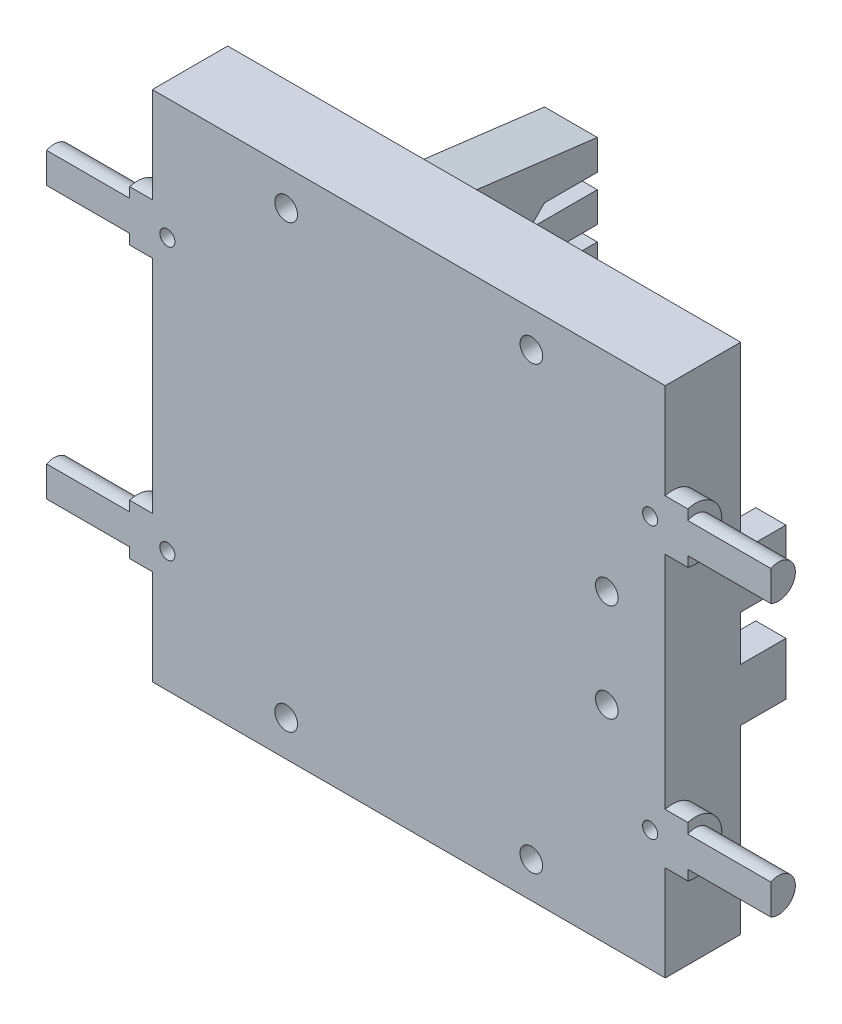
SolidWorks part; units mm, degrees
ref_plane "Front Plane" through (0, 0, 0) normal (0, 0, 1) x (1, 0, 0)
ref_plane "Top Plane" through (0, 0, 0) normal (0, 1, 0) x (1, 0, 0)
ref_plane "Right Plane" through (0, 0, 0) normal (1, 0, 0) x (0, 0, -1)
sketch "Sketch1" plane through (0, 0, 0) normal (0, 0, 1) x (1, 0, 0)
  line L1 (0, 0) -> (-68, 0)
  line L2 (0, 0) -> (0, -68)
  line L3 (0, -68) -> (-68, -68)
  line L4 (-68, 0) -> (-68, -68)
  dimension "D1" = 68
  dimension "D2" = 68
extrude "Boss-Extrude1" add sketch "Sketch1" along normal blind 10
sketch "Sketch2" plane through (-68, 0, 0) normal (-1, 0, 0) x (0, 0, 1)
  line L1 (10, 0) -> (0, 0) construction
  line L2 (10, -68) -> (0, -68) construction
  line L3 (10, 0) -> (10, -68) construction
  line L4 (10, 0) -> (10, -68)
  circle A0 centre (9, -52) radius 3.5
  circle A1 centre (9, -16) radius 3.5
  dimension "D1" = 7
  dimension "D2" = 7
  dimension "D3" = 1
  dimension "D4" = 0
  dimension "D5" = 16
  dimension "D6" = 16
extrude "Boss-Extrude2" add sketch "Sketch2" along normal blind 3 contours L4 A1 | L4 A0 region at (-68, -52, 8.0379) region at (-68, -16, 8.0379)
sketch "Sketch3" plane through (-71, 0, 0) normal (-1, 0, 0) x (0, 0, 1)
  line L0 (10, -55.3541) -> (10, -12.6459)
  circle A0 centre (9, -52) radius 2.25
  circle A1 centre (9, -16) radius 2.25
  dimension "D1" = 4.5
  dimension "D2" = 4.5
extrude "Boss-Extrude3" add sketch "Sketch3" along normal blind 11 contours L0 A0 | L0 A1 region at (-71, -52, 8.5562) region at (-71, -16, 8.5562)
sketch "Sketch4" plane through (0, 0, 0) normal (1, 0, 0) x (0, 0, -1)
  line L0 (-10, 0) -> (0, 0) construction
  line L1 (-10, -68) -> (0, -68) construction
  line L2 (-10, 0) -> (-10, -68)
  circle A0 centre (-9, -16) radius 3.5
  circle A1 centre (-9, -52) radius 3.5
  dimension "D1" = 16
  dimension "D2" = 16
  dimension "D3" = 7
  dimension "D4" = 7
  dimension "D5" = 1
  dimension "D6" = 0
extrude "Boss-Extrude4" add sketch "Sketch4" along normal blind 3 contours L2 A0 | L2 A1 region at (0, -16, 8.0379) region at (0, -52, 8.0379)
sketch "Sketch5" plane through (3, 0, 0) normal (1, 0, 0) x (0, 0, -1)
  line L0 (-10, -12.6459) -> (-10, -55.3541)
  circle A0 centre (-9, -16) radius 2.25
  circle A1 centre (-9, -52) radius 2.25
  dimension "D1" = 4.5
  dimension "D2" = 4.5
extrude "Boss-Extrude5" add sketch "Sketch5" along normal blind 11 contours L0 A0 | L0 A1 region at (3, -16, 8.5562) region at (3, -52, 8.5562)
sketch "Sketch6" plane through (0, 0, 0) normal (0, 0, -1) x (-1, 0, 0)
  line L0 (0, -34) -> (68, -34) construction
  line L1 (55.25, -12.75) -> (12.75, -12.75)
  line L2 (55.25, -12.75) -> (55.25, -55.25)
  line L3 (55.25, -55.25) -> (12.75, -55.25)
  line L4 (12.75, -12.75) -> (12.75, -55.25)
  line L5 (0, -68) -> (0, 0) construction
  line L6 (68, 0) -> (68, -68) construction
  line L7 (34, 0) -> (34, -68) construction
  line L8 (0, 0) -> (68, 0) construction
  line L9 (68, -68) -> (0, -68) construction
  point P16 (12.75, -34)
  point P17 (34, -55.25)
  dimension "D1" = 42.5
  dimension "D2" = 42.5
  dimension "D3" = 0
  dimension "D4" = 0
extrude "Cut-Extrude1" cut sketch "Sketch6" against normal blind 3
sketch "Sketch8" plane through (0, 0, 0) normal (0, 0, -1) x (-1, 0, 0)
  line L0 (55.25, -12.75) -> (12.75, -12.75) construction
  line L2 (12.75, -12.75) -> (12.75, -55.25) construction
  line L3 (34, 0) -> (34, -108.8236) construction
  line L4 (0, 0) -> (68, 0) construction
  line L5 (0, -34) -> (112.3527, -34) construction
  line L6 (0, -68) -> (0, 0) construction
  circle A0 centre (17.75, -4.75) radius 1.5
  circle A3 centre (50.25, -4.75) radius 1.5
  circle A4 centre (50.25, -63.25) radius 1.5
  circle A5 centre (17.75, -63.25) radius 1.5
  dimension "D1" = 8
  dimension "D3" = 3
  dimension "D5" = 5
extrude "Cut-Extrude2" cut sketch "Sketch8" against normal blind 15
sketch "Sketch9" plane through (0, 0, 0) normal (0, 0, -1) x (-1, 0, 0)
  line L1 (0, -24) -> (4, -24)
  line L2 (0, -24) -> (0, -31)
  line L3 (0, -31) -> (4, -31)
  line L4 (4, -24) -> (4, -31)
  line L5 (0, -68) -> (0, 0) construction
  line L6 (0, -34) -> (68, -34) construction
  line L7 (68, 0) -> (68, -68) construction
  line L8 (0, -37) -> (4, -37)
  line L9 (4, -44) -> (4, -37)
  line L10 (0, -44) -> (4, -44)
  line L11 (0, -44) -> (0, -37)
  point P6 (0, -34)
  dimension "D1" = 4
  dimension "D2" = 7
  dimension "D3" = 0
  dimension "D4" = 3
extrude "Boss-Extrude6" add sketch "Sketch9" along normal blind 6
sketch "Sketch10" plane through (0, 0, 0) normal (0, 0, -1) x (-1, 0, 0)
  line L0 (0, -34) -> (23.3312, -34) construction
  line L1 (0, -37) -> (0, -31) construction
  line L2 (12.75, -12.75) -> (12.75, -55.25) construction
  line L3 (4, -31) -> (4, -24) construction
  circle A0 centre (7.75, -27.5) radius 1.5
  circle A1 centre (7.75, -40.5) radius 1.5
  point P10 (4, -27.5)
  dimension "D1" = 3
  dimension "D2" = 5
  dimension "D3" = 0
extrude "Cut-Extrude3" cut sketch "Sketch10" against normal blind 10
sketch "Sketch11" plane through (0, 0, 10) normal (0, 0, 1) x (1, 0, 0)
  line L0 (-68, -34) -> (19.7059, -34) construction
  line L1 (-68, -19.3541) -> (-68, -48.6459) construction
  line L2 (-34, -68) -> (-34, 32.0149) construction
  line L3 (-68, -68) -> (0, -68) construction
  line L4 (-82, -54.0156) -> (-82, -49.9844) construction
  circle A0 centre (-66, -52) radius 1
  circle A1 centre (-66, -16) radius 1
  circle A2 centre (-2, -52) radius 1
  circle A3 centre (-2, -16) radius 1
  point P12 (-82, -52)
  dimension "D1" = 16
  dimension "D2" = 0
  dimension "D3" = 2
extrude "Cut-Extrude4" cut sketch "Sketch11" against normal blind 20
sketch "Sketch13" plane through (0, 0, 0) normal (0, 0, -1) x (-1, 0, 0)
  line L0 (68, 0) -> (68, -68) construction
  line L1 (59, -26) -> (66, -26)
  line L2 (59, -26) -> (59, -42)
  line L3 (59, -42) -> (66, -42)
  line L4 (66, -26) -> (66, -42)
  point P4 (66, -34)
  point P7 (68, -34)
  dimension "D1" = 7
  dimension "D2" = 0
  dimension "D3" = 16
  dimension "D4" = 2
extrude "Boss-Extrude7" add sketch "Sketch13" along normal blind 40
sketch "Sketch15" plane through (-66, 0, 0) normal (-1, 0, 0) x (0, 0, 1)
  line L0 (-40, -34) -> (24.0661, -34) construction
  line L1 (-40, -42) -> (-40, -26) construction
  line L2 (-40, -32) -> (-31, -32)
  line L3 (-31, -32) -> (-33, -30)
  line L4 (-33, -30) -> (-40, -30)
  line L5 (-40, -30) -> (-40, -32)
  line L6 (-40, -26) -> (0, -26) construction
  line L7 (-40, -38) -> (-40, -36)
  line L8 (-31, -36) -> (-33, -38)
  line L9 (-33, -38) -> (-40, -38)
  line L10 (-40, -36) -> (-31, -36)
  dimension "D1" = 2
  dimension "D2" = 4
  dimension "D3" = 45
  dimension "D4" = 7
extrude "Cut-Extrude5" cut sketch "Sketch15" against normal blind 10
sketch "Sketch16" plane through (-66, 0, 0) normal (-1, 0, 0) x (0, 0, 1)
  line L0 (0, -26) -> (-40, -26)
  line L1 (-40, -26) -> (0, -21)
  line L2 (0, -21) -> (0, -26)
  line L3 (-40, -34) -> (21.219, -34) construction
  line L4 (-40, -36) -> (-40, -32) construction
  line L5 (-40, -42) -> (0, -47)
  line L6 (0, -42) -> (-40, -42)
  line L7 (0, -47) -> (0, -42)
  dimension "D1" = 5
extrude "Boss-Extrude8" add sketch "Sketch16" against normal up to vertex (7 mm away) up to point (-59, -26, -40)
